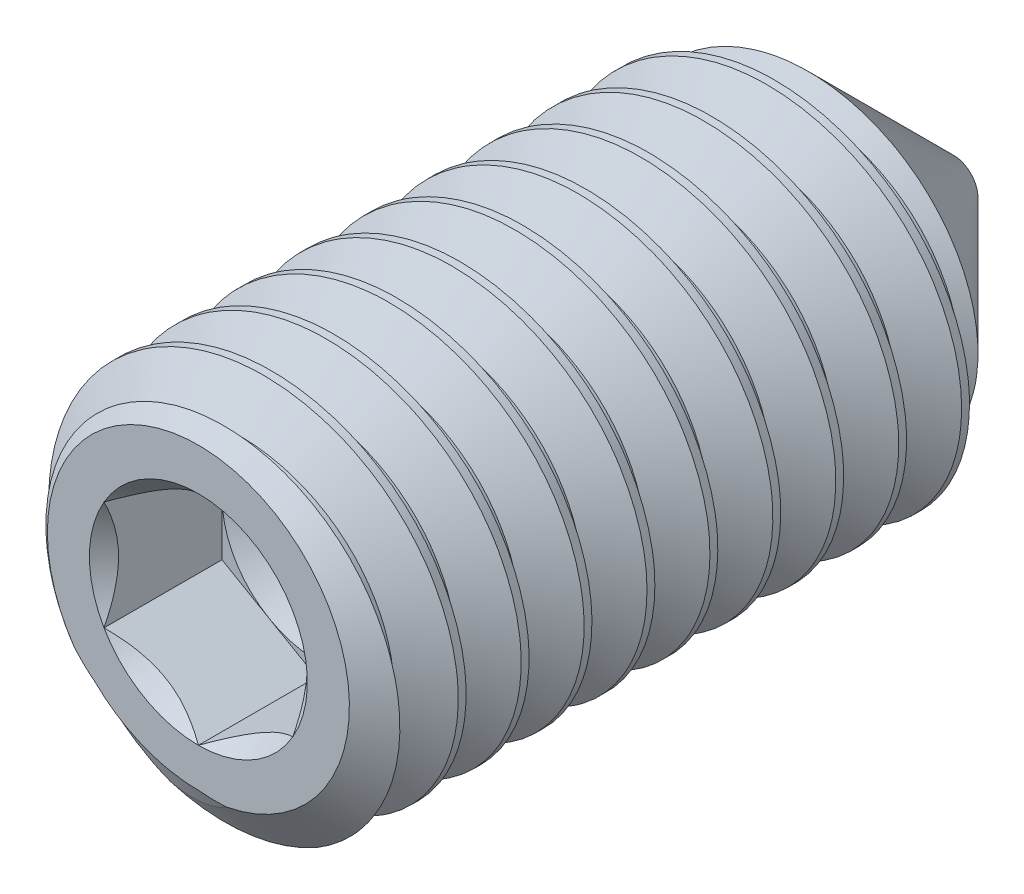
SolidWorks part; units mm, degrees
ref_plane "Front" through (0, 0, 0) normal (0, 0, 1) x (1, 0, 0)
ref_plane "Top" through (0, 0, 0) normal (0, 1, 0) x (1, 0, 0)
ref_plane "Right" through (0, 0, 0) normal (1, 0, 0) x (0, 0, -1)
ref_axis "Center Line Axis" through (0, 0, -88.8886) along (0, 0, 1)
sketch "Body Sketch" plane through (0, 0, 0) normal (1, 0, 0) x (0, 0, -1)
  line L0 (-3, 0) -> (-3, 1.2)
  line L1 (-3, 1.2) -> (-2.7899, 1.5)
  line L2 (-2.7899, 1.5) -> (1.695, 1.5)
  line L3 (1.695, 1.5) -> (3, 0.195)
  line L4 (-3, 1.2) -> (-3, -1.2) construction
  line L5 (3, 0) -> (-3, 0)
  line L6 (0, 1.5) -> (0, -1.5) construction
  line L8 (3, 0.195) -> (3, 0)
  line L9 (-3, -1.5) -> (3, -1.5) construction
  line L10 (3, 0.195) -> (3, -0.195) construction
  line L11 (3, -0.195) -> (1.695, -1.5) construction
  line L13 (3, 0.195) -> (2.805, 0) construction
  line L15 (2.805, 0) -> (3, -0.195) construction
  dimension "D3" = 35
  dimension "D7" = 2.4
  dimension "Diameter" = 3
  dimension "Length" = 6
  dimension "D2" = 0.39
  dimension "Cone Angle" = 90
  dimension "D90" = 90
revolve "Body Revolve" add sketch "Body Sketch" angle 360 about L5
ref_plane "Tip Plane" through (0, 0, -3) normal (0, 0, 1) x (1, 0, 0)
sketch "Spiral Sketch" plane through (0, 0, -3) normal (0, 0, 1) x (1, 0, 0)
  circle A0 centre (0, 0) radius 1.5 construction
  circle A1 centre (0, 0) radius 1.5
sketch "Hex Sketch" plane through (0, 0, 3) normal (0, 0, 1) x (1, 0, 0)
  line L1 (0, 0.866) -> (-0.75, 0.433)
  line L2 (-0.75, 0.433) -> (-0.75, -0.433)
  line L3 (-0.75, -0.433) -> (0, -0.866)
  line L4 (0, -0.866) -> (0.75, -0.433)
  line L5 (0.75, -0.433) -> (0.75, 0.433)
  line L6 (0.75, 0.433) -> (0, 0.866)
  circle A0 centre (0, 0) radius 0.75 construction
  dimension "Hex" = 1.5
extrude "Hex Extrude" cut sketch "Hex Sketch" against normal blind 0.9375
sketch "Hex Entry Sketch" plane through (0, 0, 3) normal (0, 0, 1) x (1, 0, 0)
  circle A0 centre (0, 0) radius 0.866
extrude "Hex Entry Extrude" cut sketch "Hex Entry Sketch" against normal through all draft 45
sketch "Hex Bottom Sketch" plane through (0, 0, 2.0625) normal (0, 0, 1) x (1, 0, 0)
  circle A0 centre (0, 0) radius 0.75 construction
  circle A1 centre (0, 0) radius 0.75
extrude "Hex Bottom Extrude" cut sketch "Hex Bottom Sketch" against normal through all draft 60
curve "Helix/Spiral" pitch 0.5 height 6.5 radius 1.5 centre (0, 0, -3) axis (0, 0, 1) start towards (0, 1, 0)
sketch "Sketch28" plane through (0, 0, 0) normal (1, 0, 0) x (0, 0, -1)
  line L0 (3, 1.5) -> (3.4375, 1.5)
  line L1 (3.4375, 1.5) -> (3.25, 1.1752)
  line L2 (3.25, 1.1752) -> (3.1875, 1.1752)
  line L3 (3.1875, 1.1752) -> (3, 1.5)
  line L4 (3.0937, 1.3376) -> (3.3437, 1.3376) construction
  line L6 (-2.7899, 1.5) -> (1.695, 1.5) construction
  line L7 (3, 6.7518) -> (3, -6.7518) construction
  dimension "D1" = 0.0625
  dimension "D3" = 60
  dimension "D2" = 0.25
sweep "Thread Sweep" cut profiles "Sketch28" path "Helix/Spiral"
ref_plane "Contact Plane 1" through (0, 0, 3) normal (0, 0, 1) x (1, 0, 0)
ref_plane "Contact Plane 2" through (0, 0, -3) normal (0, 0, -1) x (-1, 0, 0)
ref_axis "Center Axis 1" through (0, 0, 48.3835) along (0, 0, -1)
equation "\"D7@Body Sketch\" = \"Diameter@Body Sketch\" * .8"
equation "\"D1@Sketch28\" = \"D4@Helix/Spiral\" * .125"
equation "\"D3@Helix/Spiral\" = \"Length@Body Sketch\" + \"D4@Helix/Spiral\""
equation "\"hex Depth@Hex Extrude\" = \"Hex@Hex Sketch\" * .625"
equation "\"D2@Sketch28\" = \"D4@Helix/Spiral\" * .5"
equation "\"D2@Body Sketch\" = \"Diameter@Body Sketch\" * .13"
equation "\"D90@Body Sketch\" = \"Cone Angle@Body Sketch\""
equation "\"Diameter\"= 3mm"
equation "\"Thread Pitch\"= 0.5mm"
equation "\"Hex Size\"= 1.5mm"
equation "\"Diameter@Body Sketch\" = \"Diameter\""
equation "\"Hex@Hex Sketch\" = \"Hex Size\""
equation "\"D4@Helix/Spiral\"=\"Thread Pitch\""
